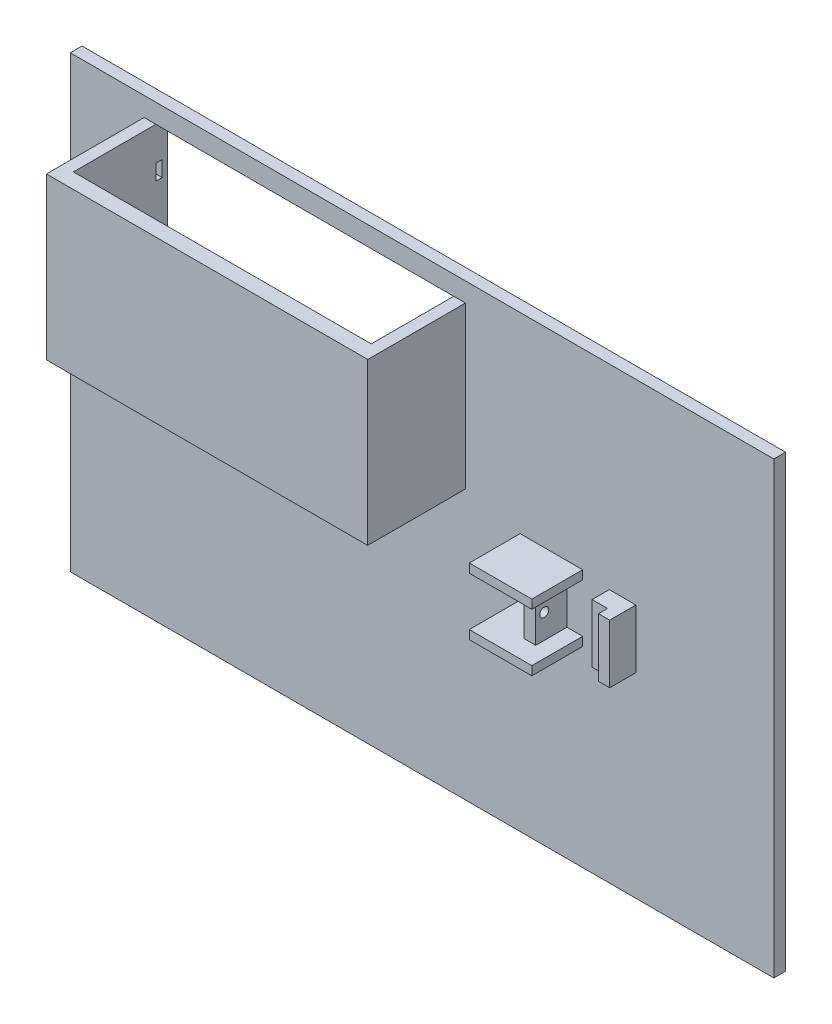
SolidWorks part; units mm, degrees
ref_plane "前视基准面" through (0, 0, 0) normal (0, 0, 1) x (1, 0, 0)
ref_plane "上视基准面" through (0, 0, 0) normal (0, 1, 0) x (1, 0, 0)
ref_plane "右视基准面" through (0, 0, 0) normal (1, 0, 0) x (0, 0, -1)
sketch "草图1" plane through (0, 0, 0) normal (0, 0, 1) x (1, 0, 0)
  line L1 (-90, 57.5) -> (90, 57.5)
  line L2 (-90, 57.5) -> (-90, -57.5)
  line L3 (-90, -57.5) -> (90, -57.5)
  line L4 (90, 57.5) -> (90, -57.5)
  line L5 (-90, 57.5) -> (90, -57.5) construction
  line L6 (-90, -57.5) -> (90, 57.5) construction
  point P0 (0, 0)
  dimension "D1" = 115
  dimension "D2" = 180
extrude "凸台-拉伸1" add sketch "草图1" along normal blind 3
sketch "草图7" plane through (0, 0, 0) normal (0, 0, -1) x (-1, 0, 0)
  line L0 (-90, 57.5) -> (90, 57.5) construction
  line L1 (-8.1, 52.6) -> (68.1, 52.6)
  line L2 (-8.1, 52.6) -> (-8.1, 11.4)
  line L3 (-8.1, 11.4) -> (68.1, 11.4)
  line L4 (68.1, 52.6) -> (68.1, 11.4)
  line L5 (90, 57.5) -> (90, -57.5) construction
  dimension "D1" = 41.2
  dimension "D2" = 76.2
  dimension "D3" = 4.9
  dimension "D4" = 21.9
extrude "电池位切除-拉伸3" cut sketch "草图7" against normal up to next
sketch "草图4" plane through (0, 0, 0) normal (0, 0, -1) x (-1, 0, 0)
  line L0 (68.1, 11.4) -> (68.1, 52.6) construction
  line L5 (68.1, 32) -> (94.8483, 32) construction
  line L10 (83.2374, -53.4277) -> (79.3374, -53.4277) construction
  line L11 (83.2374, -49.6277) -> (83.2374, -53.4277) construction
  line L12 (79.3374, -49.6277) -> (83.2374, -49.6277) construction
  line L13 (68.1, 20) -> (68.1, 24)
  line L20 (72.1, 20) -> (68.1, 20)
  line L21 (72.1, 24) -> (72.1, 20)
  line L22 (68.1, 24) -> (72.1, 24)
  line L29 (68.1, 40) -> (72.1, 40)
  line L30 (72.1, 40) -> (72.1, 44)
  line L31 (72.1, 44) -> (68.1, 44)
  line L32 (68.1, 44) -> (68.1, 40)
  point P6 (70.1, 40)
  dimension "D1" = 4
  dimension "D2" = 4
  dimension "D3" = 8
extrude "切除-拉伸2" cut sketch "草图4" along normal blind 1.6 from surface starting at face at (-30, 32, 3)
sketch "草图8" plane through (0, 0, 3) normal (0, 0, 1) x (1, 0, 0)
  line L0 (-68.1, 11.4) -> (-68.1, 20) construction
  line L1 (11.1, 11.4) -> (8.1, 11.4)
  line L2 (11.1, 11.4) -> (11.1, 52.6)
  line L3 (11.1, 52.6) -> (8.1, 52.6)
  line L4 (8.1, 11.4) -> (8.1, 52.6)
  line L5 (-68.1, 11.4) -> (-71.1, 11.4)
  line L6 (-68.1, 11.4) -> (-68.1, 52.6)
  line L7 (-68.1, 52.6) -> (-71.1, 52.6)
  line L8 (-71.1, 11.4) -> (-71.1, 52.6)
  line L9 (-68.1, 52.6) -> (8.1, 52.6) construction
  line L10 (8.1, 11.4) -> (-68.1, 11.4) construction
  line L11 (8.1, 52.6) -> (8.1, 11.4) construction
  dimension "D1" = 3
extrude "凸台-拉伸2" add sketch "草图8" along normal blind 25
sketch "草图9" plane through (0, 0, 28) normal (0, 0, 1) x (1, 0, 0)
  line L1 (11.1, 11.4) -> (-71.1, 11.4)
  line L2 (11.1, 11.4) -> (11.1, 52.6)
  line L3 (11.1, 52.6) -> (-71.1, 52.6)
  line L4 (-71.1, 11.4) -> (-71.1, 52.6)
extrude "凸台-拉伸3" add sketch "草图9" against normal blind 3.9
sketch "草图10" plane through (0, 0, 3) normal (0, 0, 1) x (1, 0, 0)
  line L0 (47.9, -0.7) -> (47.9, 61.65) construction
  line L1 (54.7, -7.5) -> (47.9, -7.5)
  line L2 (54.7, -7.5) -> (54.7, 7.5)
  line L3 (54.7, 7.5) -> (47.9, 7.5)
  line L4 (47.9, -7.5) -> (47.9, 7.5)
  line L7 (15, 9.5) -> (71.1, 9.5) construction
  dimension "D1" = 15
  dimension "D2" = 6.8
  dimension "D3" = 2
extrude "变速杆凸台-拉伸4" add sketch "草图10" along normal offset from surface (4.4 mm away) 0.1
sketch "草图11" plane through (0, 0, 7.4) normal (0, 0, 1) x (1, 0, 0)
  line L0 (54.7, -7.5) -> (47.9, -7.5) construction
  line L1 (54.7, -7.5) -> (51.85, -7.5)
  line L2 (54.7, -7.5) -> (54.7, 7.5)
  line L3 (54.7, 7.5) -> (51.85, 7.5)
  line L4 (51.85, -7.5) -> (51.85, 7.5)
  line L5 (54.7, 7.5) -> (54.7, -7.5) construction
  line L6 (47.9, 7.5) -> (54.7, 7.5) construction
  line L7 (51.7, 61.65) -> (51.7, -0.7) construction
  dimension "D1" = 0.15
extrude "变速杆前档凸台-拉伸5" add sketch "草图11" along normal blind 2.3
sketch "草图12" plane through (0, 0, 3) normal (0, 0, 1) x (1, 0, 0)
  line L0 (39.5974, -6.096) -> (37.2352, -6.096) construction
  line L1 (37.0852, -8.5) -> (25.0852, -8.5)
  line L3 (34.0852, -6.246) -> (25.0852, -6.246)
  line L4 (25.0852, -8.5) -> (25.0852, -6.246)
  line L5 (34.0852, 6.246) -> (25.0852, 6.246)
  line L7 (37.0852, 8.5) -> (25.0852, 8.5)
  line L8 (25.0852, 6.246) -> (25.0852, 8.5)
  line L9 (37.2352, 6.096) -> (39.5974, 6.096) construction
  line L10 (15, 9.5) -> (71.1, 9.5) construction
  line L13 (37.2352, -0.635) -> (37.2352, -5.461) construction
  line L15 (37.0852, -6.246) -> (37.0852, 6.246)
  line L17 (34.0852, -6.246) -> (34.0852, 6.246)
  line L19 (37.0852, 8.5) -> (41.0852, 8.5)
  line L21 (37.0852, 6.246) -> (41.0852, 6.246)
  line L22 (41.0852, 8.5) -> (41.0852, 6.246)
  line L23 (37.0852, -6.246) -> (41.0852, -6.246)
  line L25 (37.0852, -8.5) -> (41.0852, -8.5)
  line L26 (41.0852, -6.246) -> (41.0852, -8.5)
  point P12 (38.4163, 6.096)
  dimension "D1" = 0.15
  dimension "D2" = 0.15
  dimension "D3" = 1
  dimension "D4" = 2.254
  dimension "D5" = 4
  dimension "D7" = 0.15
  dimension "D8" = 3
  dimension "D9" = 9
extrude "变速舵机底座凸台-拉伸6" add sketch "草图12" along normal offset from surface (8.004 mm away) 0.1
sketch "草图13" plane through (0, 0, 11.004) normal (0, 0, 1) x (1, 0, 0)
  line L0 (25.0852, -8.5) -> (41.0852, -8.5) construction
  line L1 (25.0852, -8.5) -> (41.0852, -8.5)
  line L2 (34.0852, -6.246) -> (25.0852, -6.246) construction
  line L3 (34.0852, -6.246) -> (25.0852, -6.246)
  line L4 (41.0852, -8.5) -> (41.0852, -6.246) construction
  line L5 (41.0852, -8.5) -> (41.0852, -6.246)
  line L6 (25.0852, -6.246) -> (25.0852, -8.5) construction
  line L7 (25.0852, -6.246) -> (25.0852, -8.5)
  line L8 (41.0852, 8.5) -> (25.0852, 8.5) construction
  line L9 (41.0852, 8.5) -> (25.0852, 8.5)
  line L10 (25.0852, 8.5) -> (25.0852, 6.246) construction
  line L11 (25.0852, 8.5) -> (25.0852, 6.246)
  line L12 (25.0852, 6.246) -> (34.0852, 6.246) construction
  line L13 (25.0852, 6.246) -> (34.0852, 6.246)
  line L14 (41.0852, 6.246) -> (41.0852, 8.5) construction
  line L15 (41.0852, 6.246) -> (41.0852, 8.5)
  line L16 (34.0852, -6.246) -> (41.0852, -6.246)
  line L17 (34.0852, 6.246) -> (41.0852, 6.246)
extrude "变速舵机卡位凸台-拉伸7" add sketch "草图13" along normal blind 5
sketch "草图15" plane through (34.0852, 0, 0) normal (-1, 0, 0) x (0, 0, 1)
  circle A0 centre (8.818, 0) radius 1.15
  dimension "D1" = 2.3
extrude "变速舵机螺丝孔切除-拉伸7" cut sketch "草图15" against normal up to next
